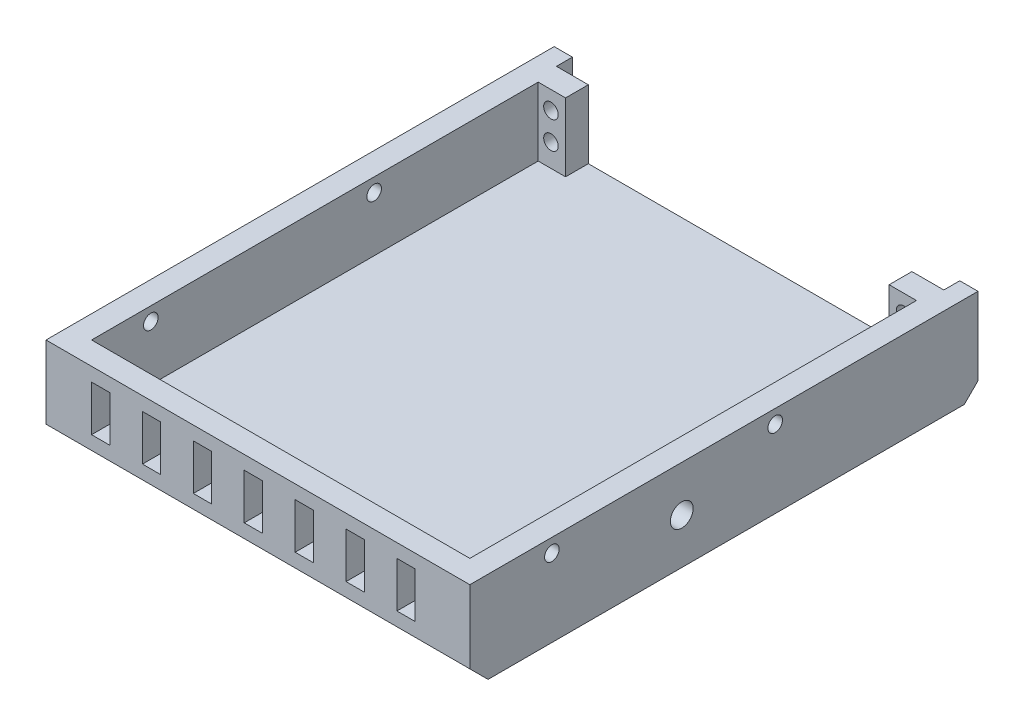
SolidWorks part; units mm, degrees
ref_plane "Alzado" through (0, 0, 0) normal (0, 0, 1) x (1, 0, 0)
ref_plane "Planta" through (0, 0, 0) normal (0, 1, 0) x (1, 0, 0)
ref_plane "Vista lateral" through (0, 0, 0) normal (1, 0, 0) x (0, 0, -1)
sketch "Croquis1" plane through (0, 0, 0) normal (0, 1, 0) x (1, 0, 0)
  line L1 (-46.5, -54) -> (46.5, -54)
  line L2 (-46.5, -54) -> (-46.5, 54)
  line L3 (-46.5, 54) -> (46.5, 54)
  line L4 (46.5, -54) -> (46.5, 54)
  line L5 (-46.5, -54) -> (46.5, 54) construction
  line L6 (-46.5, 54) -> (46.5, -54) construction
  point P0 (0, 0)
  dimension "D1" = 108
  dimension "D2" = 93
extrude "Saliente-Extruir1" add sketch "Croquis1" along normal blind 20
shell "Vaciado1" thickness 5 removed face at (0, 20, 0)
sketch "Croquis3" plane through (-46.5, 0, 0) normal (-1, 0, 0) x (0, 0, 1)
  line L0 (36, 17) -> (-13, 17) construction
  line L1 (54, 20) -> (54, 0) construction
  line L2 (-54, 20) -> (54, 20) construction
  circle A0 centre (36, 17) radius 1.6
  circle A1 centre (-13, 17) radius 1.6
  dimension "D1" = 3.2
  dimension "D2" = 3.2
  dimension "D3" = 49
  dimension "D4" = 18
  dimension "D5" = 3
extrude "Cortar-Extruir1" cut sketch "Croquis3" against normal blind 93
sketch "Croquis4" plane through (0, 0, -54) normal (0, 0, -1) x (-1, 0, 0)
  line L0 (-46.5, 20) -> (46.5, 20) construction
  line L1 (-41.5, 20) -> (41.5, 20)
  line L2 (-41.5, 20) -> (-41.5, 5)
  line L3 (-41.5, 5) -> (41.5, 5)
  line L4 (41.5, 20) -> (41.5, 5)
  line L5 (-46.5, 0) -> (46.5, 0) construction
  line L6 (46.5, 20) -> (46.5, 0) construction
  line L7 (-46.5, 20) -> (-46.5, 0) construction
  dimension "D1" = 5
  dimension "D2" = 5
  dimension "D3" = 5
extrude "Cortar-Extruir2" cut sketch "Croquis4" against normal blind 5
sketch "Croquis5" plane through (-41.5, 0, 0) normal (1, 0, 0) x (0, 0, -1)
  line L0 (-54, 20) -> (54, 20) construction
  line L1 (49, 20) -> (54, 20)
  line L2 (49, 20) -> (49, 5)
  line L3 (49, 5) -> (54, 5)
  line L4 (54, 20) -> (54, 5)
  dimension "D1" = 5
extrude "Saliente-Extruir2" add sketch "Croquis5" along normal blind 6
mirror "Simetría1" about plane through (0, 0, 0) normal (1, 0, 0) of "Saliente-Extruir2"
sketch "Croquis6" plane through (0, 0, -54) normal (0, 0, -1) x (-1, 0, 0)
  line L0 (-38.7, 16) -> (-38.7, 10) construction
  line L1 (-46.5, 20) -> (-35.5, 20) construction
  line L2 (-35.5, 5) -> (-35.5, 20) construction
  circle A0 centre (-38.7, 16) radius 1.6
  circle A1 centre (-38.7, 10) radius 1.6
  dimension "D1" = 3.2
  dimension "D2" = 3.2
  dimension "D3" = 4
  dimension "D4" = 6
  dimension "D5" = 3.2
extrude "Cortar-Extruir3" cut sketch "Croquis6" against normal up to next
mirror "Simetría2" about plane through (0, 0, 0) normal (1, 0, 0) of "Cortar-Extruir3"
sketch "Croquis7" plane through (0, 0, 0) normal (0, 1, 0) x (1, 0, 0)
  line L0 (35, 57.5) -> (31, 57.5) construction
  line L1 (46.5, 57.5) -> (42.5, 57.5)
  line L2 (46.5, 57.5) -> (46.5, 54)
  line L3 (46.5, 54) -> (42.5, 54)
  line L4 (42.5, 57.5) -> (42.5, 54)
  dimension "D1" = 4
extrude "Saliente-Extruir3" add sketch "Croquis7" along normal up to surface (20 mm away) up to face at (0, 20, -17.1667)
chamfer "Chaflán1" distance 3 angle 45 1 edges at (44.5, 0, -57.5)
mirror "Simetría3" about plane through (0, 0, 0) normal (1, 0, 0) of "Chaflán1", "Saliente-Extruir3"
chamfer "Chaflán2" distance 4 angle 45 1 edges at (0, 0, 54)
sketch "Croquis8" plane through (0, 0, 54) normal (0, 0, 1) x (1, 0, 0)
  line L0 (46.5, 12) -> (-46.5, 12) construction
  line L1 (46.5, 20) -> (46.5, 4) construction
  line L2 (-46.5, 20) -> (-46.5, 4) construction
  line L4 (34.5, 7) -> (30.5, 7)
  line L5 (34.5, 7) -> (34.5, 17)
  line L6 (34.5, 17) -> (30.5, 17)
  line L7 (30.5, 7) -> (30.5, 17)
  point P10 (30.5, 12)
  dimension "D1" = 4
  dimension "D2" = 10
  dimension "D3" = 12
extrude "Cortar-Extruir4" cut sketch "Croquis8" against normal up to next
pattern_linear "MatrizL1" count 7 spacing 11.1667 along (-1, 0, 0) of "Cortar-Extruir4"
sketch "Croquis9" plane through (0, 0, 0) normal (0, -1, 0) x (1, 0, 0)
  line L0 (0, 50) -> (0, -54) construction
  line L1 (46.5, 50) -> (-46.5, 50) construction
  line L2 (42.5, -54) -> (-42.5, -54) construction
  text T0 "DidacTech\r\nIMT" font "Century Gothic" height in points 50
extrude "Saliente-Extruir4" add sketch "Croquis9" along normal blind 4
sketch "Croquis10" plane through (46.5, 0, 0) normal (1, 0, 0) x (0, 0, -1)
  line L0 (-54, 20) -> (57.5, 20) construction
  line L1 (57.5, 20) -> (57.5, 3) construction
  circle A0 centre (-7.5, 10) radius 2.5
  dimension "D1" = 5
  dimension "D2" = 10
  dimension "D3" = 65
extrude "Cortar-Extruir5" cut sketch "Croquis10" against normal up to next
